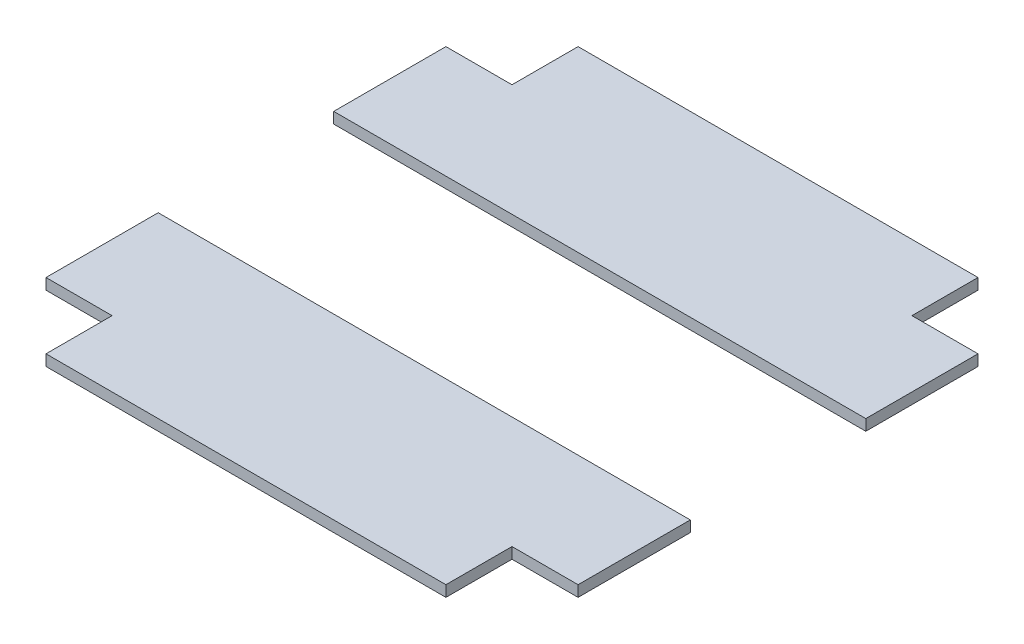
SolidWorks part; units mm, degrees
ref_plane "Front" through (0, 0, 0) normal (0, 0, 1) x (1, 0, 0)
ref_plane "Top" through (0, 0, 0) normal (0, 1, 0) x (1, 0, 0)
ref_plane "Right" through (0, 0, 0) normal (1, 0, 0) x (0, 0, -1)
sketch "Sketch1" plane through (0, 0, 0) normal (0, 1, 0) x (1, 0, 0)
  line L1 (-2454.275, 2454.275) -> (2454.275, 2454.275)
  line L2 (-2454.275, 2454.275) -> (-2454.275, -2454.275)
  line L3 (-2454.275, -2454.275) -> (2454.275, -2454.275)
  line L4 (2454.275, 2454.275) -> (2454.275, -2454.275)
  line L5 (-2454.275, 2454.275) -> (2454.275, -2454.275) construction
  line L6 (-2454.275, -2454.275) -> (2454.275, 2454.275) construction
  point P0 (0, 0)
  dimension "D1" = 4908.55
  dimension "D2" = 4908.55
extrude "Boss-Extrude1" add sketch "Sketch1" along normal blind 101.6
sketch "Sketch2" plane through (0, 101.6, 0) normal (0, 1, 0) x (1, 0, 0)
  line L0 (-2454.275, 2454.275) -> (-2454.275, -2454.275) construction
  line L1 (2454.275, -809.625) -> (-2454.275, -809.625)
  line L2 (2454.275, -809.625) -> (2454.275, 809.625)
  line L3 (2454.275, 809.625) -> (-2454.275, 809.625)
  line L4 (-2454.275, -809.625) -> (-2454.275, 809.625)
  line L5 (2454.275, -809.625) -> (-2454.275, 809.625) construction
  line L6 (2454.275, 809.625) -> (-2454.275, -809.625) construction
  point P0 (0, 0)
  dimension "D1" = 1619.25
extrude "Cut-Extrude1" cut sketch "Sketch2" against normal through all
sketch "Sketch3" plane through (0, 101.6, 0) normal (0, 1, 0) x (1, 0, 0)
  line L1 (-2454.275, -2454.275) -> (-1844.675, -2454.275)
  line L2 (-2454.275, -2454.275) -> (-2454.275, -1844.675)
  line L3 (-2454.275, -1844.675) -> (-1844.675, -1844.675)
  line L4 (-1844.675, -2454.275) -> (-1844.675, -1844.675)
  line L5 (2454.275, -2454.275) -> (1844.675, -2454.275)
  line L6 (2454.275, -2454.275) -> (2454.275, -1844.675)
  line L7 (2454.275, -1844.675) -> (1844.675, -1844.675)
  line L8 (1844.675, -2454.275) -> (1844.675, -1844.675)
  line L9 (-2454.275, 2454.275) -> (-1844.675, 2454.275)
  line L10 (-2454.275, 2454.275) -> (-2454.275, 1844.675)
  line L11 (-2454.275, 1844.675) -> (-1844.675, 1844.675)
  line L12 (-1844.675, 2454.275) -> (-1844.675, 1844.675)
  line L13 (2454.275, 2454.275) -> (1844.675, 2454.275)
  line L14 (2454.275, 2454.275) -> (2454.275, 1844.675)
  line L15 (2454.275, 1844.675) -> (1844.675, 1844.675)
  line L16 (1844.675, 2454.275) -> (1844.675, 1844.675)
  dimension "D1" = 609.6
extrude "Cut-Extrude2" cut sketch "Sketch3" against normal through all
